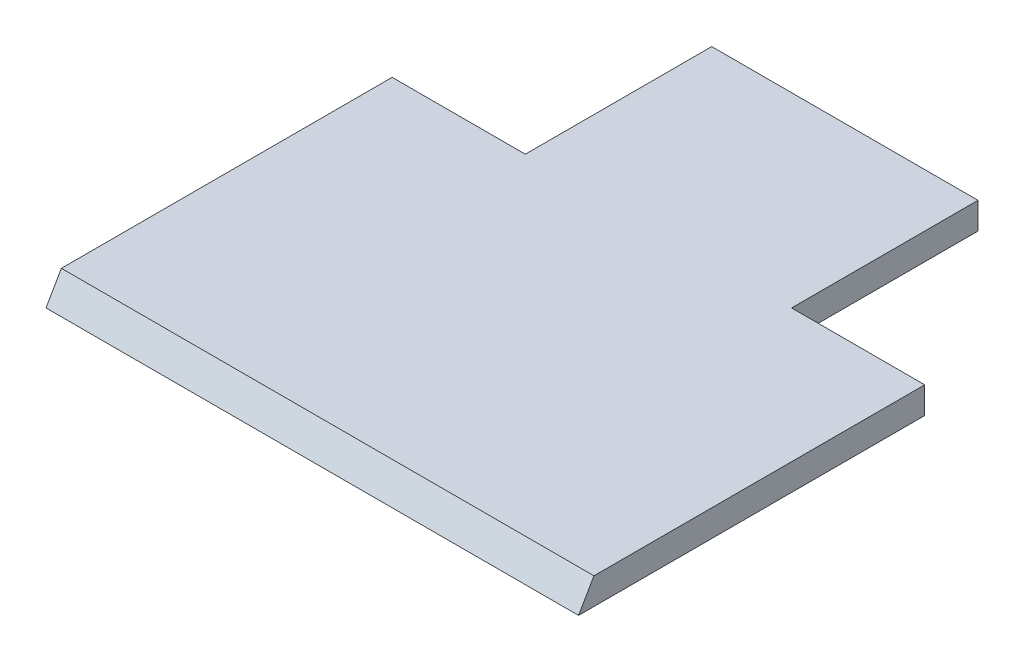
SolidWorks part; units mm, degrees
ref_plane "Alzado" through (0, 0, 0) normal (0, 0, 1) x (1, 0, 0)
ref_plane "Planta" through (0, 0, 0) normal (0, 1, 0) x (1, 0, 0)
ref_plane "Vista lateral" through (0, 0, 0) normal (1, 0, 0) x (0, 0, -1)
sketch "Croquis1" plane through (0, 0, 0) normal (0, 1, 0) x (1, 0, 0)
  line L1 (-50, -50) -> (50, -50)
  line L2 (-50, -50) -> (-50, 50)
  line L3 (-50, 50) -> (50, 50)
  line L4 (50, -50) -> (50, 50)
  line L5 (-50, -50) -> (50, 50) construction
  line L6 (-50, 50) -> (50, -50) construction
  point P0 (0, 0)
  dimension "D1" = 100
  dimension "D2" = 100
extrude "Saliente-Extruir1" add sketch "Croquis1" along normal blind 5
chamfer "Chaflán1" distance 5 angle 30 1 edges at (0, 5, 50) first distance on face at (0, 2.5, 50)
sketch "Croquis2" plane through (0, 5, 0) normal (0, 1, 0) x (1, 0, 0)
  line L1 (-50, 50) -> (-25, 50)
  line L2 (-50, 50) -> (-50, 15)
  line L3 (-50, 15) -> (-25, 15)
  line L4 (-25, 50) -> (-25, 15)
  line L5 (50, 50) -> (25, 50)
  line L6 (50, 50) -> (50, 15)
  line L7 (50, 15) -> (25, 15)
  line L8 (25, 50) -> (25, 15)
  dimension "D1" = 25
  dimension "D2" = 25
  dimension "D3" = 35
  dimension "D4" = 35
extrude "Cortar-Extruir1" cut sketch "Croquis2" against normal up to next
